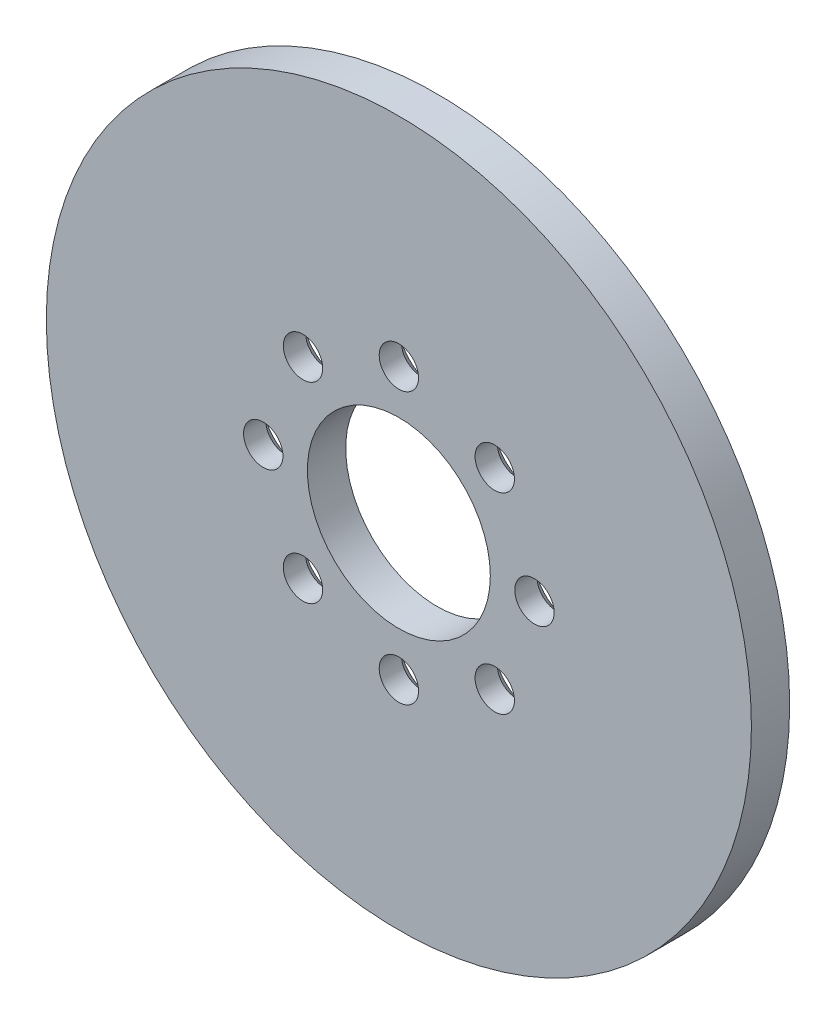
SolidWorks part; units mm, degrees
material "AISI Type A2 Tool Steel"
ref_plane "Front Plane" through (0, 0, 0) normal (0, 0, 1) x (1, 0, 0)
ref_plane "Top Plane" through (0, 0, 0) normal (0, 1, 0) x (1, 0, 0)
ref_plane "Right Plane" through (0, 0, 0) normal (1, 0, 0) x (0, 0, -1)
sketch "Sketch1" plane through (0, 0, 0) normal (0, 0, 1) x (1, 0, 0)
  line L0 (0, 0) -> (0, 22.5) construction
  line L1 (0, 0) -> (-39.3193, 27.5317) construction
  line L2 (0, 0) -> (39.3193, 27.5317) construction
  line L3 (-39.3193, 27.5317) -> (-22.9363, 16.0601)
  line L4 (39.3193, 27.5317) -> (22.9363, 16.0601)
  line L5 (43.5028, 20.2857) -> (25.3766, 11.8333)
  line L6 (4.1835, -47.8173) -> (2.4404, -27.8935)
  line L7 (-4.1835, -47.8173) -> (-2.4404, -27.8935)
  line L8 (-43.5028, 20.2857) -> (-25.3766, 11.8333)
  circle A0 centre (0, 0) radius 58.5
  circle A1 centre (0, 0) radius 22.5 construction
  circle A2 centre (0, 22.5) radius 3.2639
  circle A3 centre (15.9099, 15.9099) radius 3.2639
  circle A4 centre (22.5, 0) radius 3.2639
  circle A5 centre (15.9099, -15.9099) radius 3.2639
  circle A6 centre (0, -22.5) radius 3.2639
  circle A7 centre (-15.9099, -15.9099) radius 3.2639
  circle A8 centre (-22.5, 0) radius 3.2639
  circle A9 centre (-15.9099, 15.9099) radius 3.2639
  arc A10 (-39.3193, 27.5317) -> (39.3193, 27.5317) centre (0, 0) cw
  arc A11 (-22.9363, 16.0601) -> (22.9363, 16.0601) centre (0, 0) cw
  arc A12 (43.5028, 20.2857) -> (4.1835, -47.8173) centre (0, 0) cw
  arc A13 (25.3766, 11.8333) -> (2.4404, -27.8935) centre (0, 0) cw
  arc A14 (-4.1835, -47.8173) -> (-43.5028, 20.2857) centre (0, 0) cw
  arc A15 (-2.4404, -27.8935) -> (-25.3766, 11.8333) centre (0, 0) cw
  circle A16 centre (0, 0) radius 15.175
  point P4 (0, 22.5)
  point P8 (15.9099, 15.9099)
  point P9 (22.5, 0)
  point P10 (15.9099, -15.9099)
  point P11 (0, -22.5)
  point P12 (-15.9099, -15.9099)
  point P13 (-22.5, 0)
  point P14 (-15.9099, 15.9099)
  point P15 (0, 0)
  point P43 (0, 0)
  dimension "D1" = 117
  dimension "D2" = 45
  dimension "D4" = 6.5278
  dimension "D6" = 28
  dimension "D7" = 20
  dimension "D9" = 30.35
  dimension "D5" = 110
  dimension "D3" = 8
  dimension "D8" = 3
extrude "Boss-Extrude1" add sketch "Sketch1" along normal blind 6.35 contours L7 A15 L8 A14 | L3 A11 L4 A10 | L5 A13 L6 A12 | A0 A16 A15 L7 A14 L8 A13 L5 A12 L6 A11 L3 A10 L4 A9 A8 A7 A6 A5 A4 A3 A2 region at (0, 33.1756, 0) region at (28.731, -16.5878, 0) region at (-28.731, -16.5878, 0) region at (-56.8454, 0, 0)
sketch "Sketch3" plane through (0, 0, 0) normal (0, 0, -1) x (-1, 0, 0)
  point P0 (-15.9099, 15.9099)
  point P3 (0, 22.5)
  point P6 (15.9099, 15.9099)
  point P9 (22.5, 0)
  point P12 (15.9099, -15.9099)
  point P15 (0, -22.5)
  point P18 (-15.9099, -15.9099)
  point P21 (-22.5, 0)
hole_wizard "CSK for 1/4 Flat Head Machine Screw (100)1" positions "Sketch3" profile "Sketch4" countersink size "1/4" standard "ANSI Inch"
sketch "Sketch4" plane through (15.9099, 15.9099, 0) normal (1, 0, 0) x (0, 1, 0)
  line L0 (0, 0) -> (0, 56.0711)
  line L1 (0, 56.0711) -> (3.2639, 54.11)
  line L2 (3.2639, 54.11) -> (3.2639, 2.6641)
  line L3 (3.2639, 2.6641) -> (6.4389, 0)
  line L5 (6.4389, 0) -> (0, 0)
  line L6 (-3.2639, 2.6641) -> (-6.4389, 0) construction
  line L10 (0, 56.0711) -> (-3.2639, 54.11) construction
  line L11 (0, -6.35) -> (0, 107.95) construction
  dimension "Hole Dia." = 6.5278
  dimension "Hole Depth" = 54.11
  dimension "Near C'Sink Dia." = 12.8778
  dimension "Near C'Sink Angle" = 100
  dimension "Drill Angle" = 118
